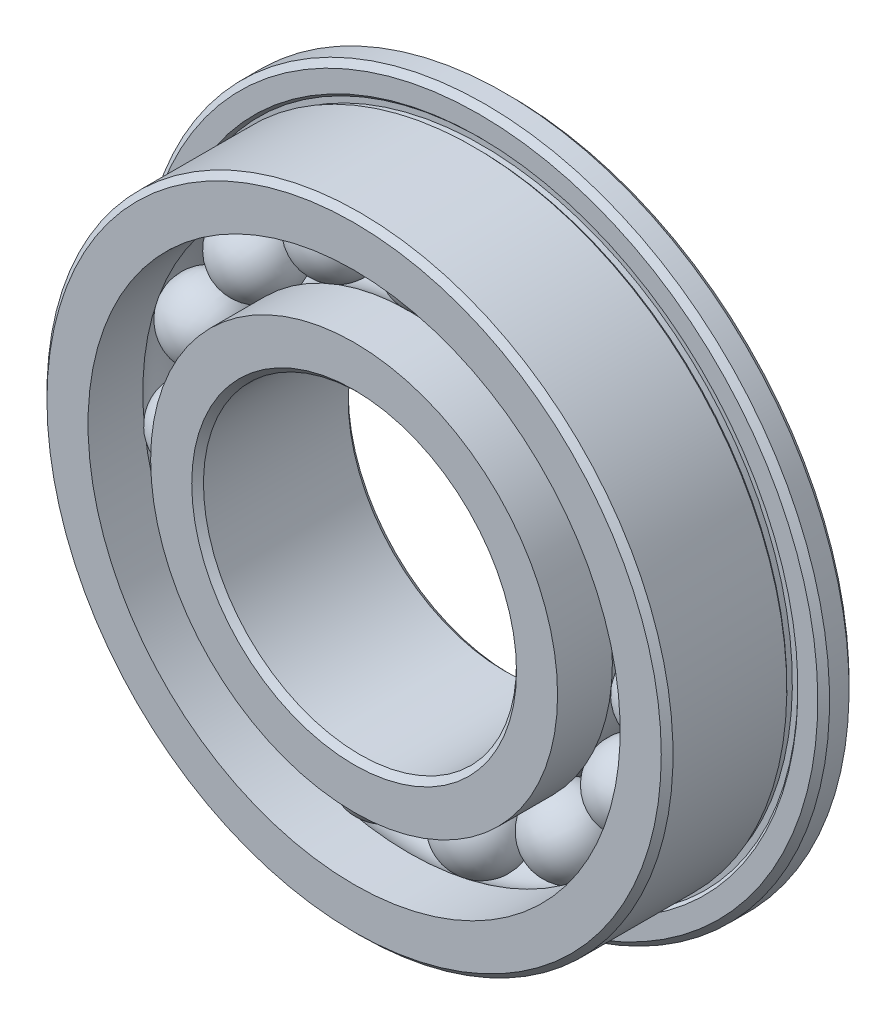
SolidWorks part; units mm, degrees
ref_plane "Front Plane" through (0, 0, 0) normal (0, 0, 1) x (1, 0, 0)
ref_plane "Top Plane" through (0, 0, 0) normal (0, 1, 0) x (1, 0, 0)
ref_plane "Right Plane" through (0, 0, 0) normal (1, 0, 0) x (0, 0, -1)
sketch "Sketch1" plane through (0, 0, 0) normal (1, 0, 0) x (0, 0, -1)
  line L0 (0, 6) -> (0, -6) construction
  line L1 (-1.5, 6) -> (1.5, 6) construction
  line L2 (0, 0) -> (1.5, 0) construction
  line L3 (1.5, 6.6) -> (1.5, -6.6) construction
  line L4 (1.5, -6.6) -> (0.9, -6.6) construction
  line L5 (1.5, 3) -> (0, 3) construction
  line L6 (1.5, 3) -> (1.5, -3) construction
  dimension "OD" = 12
  dimension "Width" = 3
  dimension "Flange Thickness" = 0.6
  dimension "ID" = 6
  dimension "Flange OD" = 13.2
sketch "Sketch2" plane through (0, 0, 0) normal (1, 0, 0) x (0, 0, -1)
  line L0 (1.5, 6.6) -> (0.9, 6.6)
  line L1 (0.9, 6.6) -> (0.9, 6.1061)
  line L2 (0.7939, 6) -> (-1.5, 6)
  line L3 (-1.5, 6) -> (-1.5, 5.1)
  line L4 (-1.5, 5.1) -> (-0.45, 5.1)
  line L5 (1.5, 6.6) -> (1.5, -6.6) construction
  line L6 (1.5, 5.1) -> (1.5, 6.6)
  line L7 (1.5, 3) -> (-1.5, 3)
  line L8 (-1.5, 3) -> (-1.5, 3.9)
  line L9 (-1.5, 3.9) -> (-0.45, 3.9)
  line L10 (1.5, 3.9) -> (1.5, 3)
  line L11 (0, 6) -> (0, 3) construction
  line L12 (-0.75, 4.5) -> (0.75, 4.5) construction
  line L13 (0.45, 5.1) -> (1.5, 5.1)
  line L14 (0.45, 3.9) -> (1.5, 3.9)
  line L15 (0.9, 6.1061) -> (0.953, 6.053)
  line L16 (0.953, 6.053) -> (0.953, 5.947)
  line L17 (0.953, 5.947) -> (0.847, 5.947)
  line L18 (0.847, 5.947) -> (0.7939, 6)
  line L19 (0.9, 6) -> (0.953, 5.947) construction
  line L20 (0.953, 6.053) -> (0.847, 5.947) construction
  line L21 (0.7939, 6) -> (0.9, 6) construction
  line L22 (0.9, 6) -> (0.9, 6.1061) construction
  circle A0 centre (0, 4.5) radius 0.75 construction
  arc A1 (-0.45, 5.1) -> (0.45, 5.1) centre (0, 4.5) cw
  arc A2 (-0.45, 3.9) -> (0.45, 3.9) centre (0, 4.5) ccw
  dimension "D1" = 3
  dimension "Ball Dia." = 1.5
  dimension "D2" = 135
  dimension "D3" = 0.15
  dimension "D4" = 1.2
  dimension "Race Thikness" = 0.9
revolve "Revolve1" add sketch "Sketch2" angle 360 about L2
fillet "Fillet1" radius 0.1125 3 edges at (0, -6.6, -1.5) (0, -6.6, -0.9) (0, -6, 1.5) profile chamfer
sketch "Sketch3" plane through (0, 0, 0) normal (0, 0, 1) x (1, 0, 0)
  line L0 (-3, 0) -> (3, 0) construction
  line L1 (-6, 0) -> (6, 0) construction
  point P5 (0, 0)
  dimension "ID2" = 6
  dimension "OD2" = 12
fillet "Fillet2" radius 0.1125 2 edges at (0, -3, -1.5) (0, -3, 1.5) profile chamfer
sketch "Sketch7" plane through (0, 0, 0) normal (0, 0, 1) x (1, 0, 0)
  line L0 (0, 5.25) -> (0, 3.75)
  line L1 (0, 6.6) -> (0, -6.6) construction
  line L2 (-0.8874, 5.25) -> (0, 0) construction
  line L3 (0, 0) -> (0.8874, 5.25) construction
  line L4 (0.8874, 5.25) -> (-0.8874, 5.25) construction
  circle A0 centre (0, 4.5) radius 0.75 construction
  circle A1 centre (0, 0) radius 5.25 construction
  circle A2 centre (0, 0) radius 3.75 construction
  arc A4 (0, 5.25) -> (0, 3.75) centre (0, 4.5) ccw
  dimension "D1" = 19.188
revolve "Revolve3" add sketch "Sketch7" angle 360 about L0
pattern_circular "CirPattern3" count 15 over 360 about axis through (0, 0, 0) along (0, 0, -1) of bodies 107
sketch "Sketch8" plane through (0, 0, 0) normal (1, 0, 0) x (0, 0, -1)
  line L0 (-1.5, 6) -> (1.5, 6) construction
  line L1 (1.5, 6) -> (1.5, 6.6) construction
  line L2 (-1.5, -6) -> (1.5, -6) construction
  line L3 (1.5, 6.6) -> (1.5, -6.6) construction
  dimension "D1" = 12
equation "\"Ball Dia.@Sketch2\" = ( \"OD@Sketch1\" - \"ID@Sketch1\" ) * .25"
equation "\"D3@Sketch2\"=\"Flange Thickness@Sketch1\"/4"
equation "\"D1@Fillet1\" = \"Race Thikness@Sketch2\" / 8"
equation "\"ID2@Sketch3\" = \"ID@Sketch1\""
equation "\"OD2@Sketch3\" = \"OD@Sketch1\""
equation "\"D1@Fillet2\" = \"Race Thikness@Sketch2\" / 8"
equation "\"D1@CirPattern3\"=360/\"D1@Sketch7\"-4"
equation "\"D4@Sketch2\" = ( \"OD@Sketch1\" - \"ID@Sketch1\" ) * .2"
